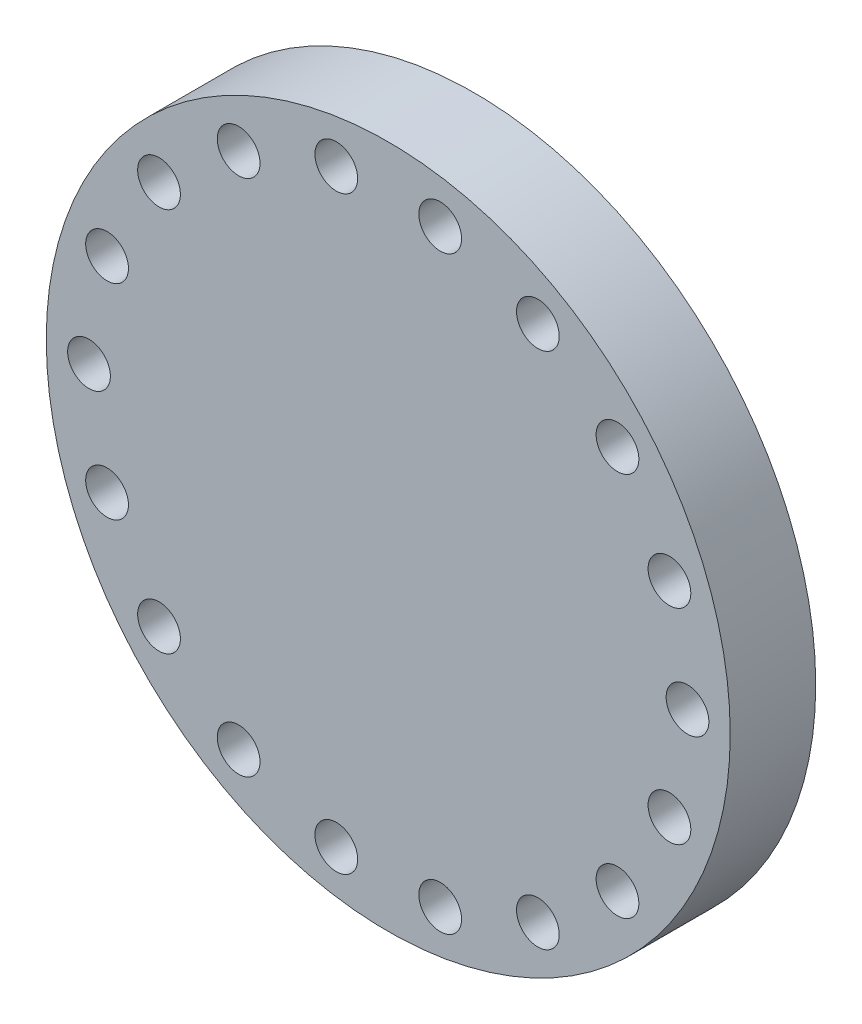
SolidWorks part; units mm, degrees
ref_plane "Front Plane" through (0, 0, 0) normal (0, 0, 1) x (1, 0, 0)
ref_plane "Top Plane" through (0, 0, 0) normal (0, 1, 0) x (1, 0, 0)
ref_plane "Right Plane" through (0, 0, 0) normal (1, 0, 0) x (0, 0, -1)
sketch "Sketch1" plane through (0, 0, 0) normal (0, 0, 1) x (1, 0, 0)
  line L0 (0, 0) -> (-44.45, 0) construction
  line L1 (0, 0) -> (-41.7693, 15.2028) construction
  circle A0 centre (0, 0) radius 50.8
  circle A1 centre (-44.45, 0) radius 3.175
  circle A2 centre (-41.7693, 15.2028) radius 3.175
  circle A3 centre (-34.0507, 28.5719) radius 3.175
  circle A4 centre (-22.225, 38.4948) radius 3.175
  circle A5 centre (-7.7187, 43.7747) radius 3.175
  circle A6 centre (7.7187, 43.7747) radius 3.175
  circle A7 centre (22.225, 38.4948) radius 3.175
  circle A8 centre (34.0507, 28.5719) radius 3.175
  circle A9 centre (41.7693, 15.2028) radius 3.175
  circle A10 centre (44.45, 0) radius 3.175
  circle A11 centre (41.7693, -15.2028) radius 3.175
  circle A12 centre (34.0507, -28.5719) radius 3.175
  circle A13 centre (22.225, -38.4948) radius 3.175
  circle A14 centre (7.7187, -43.7747) radius 3.175
  circle A15 centre (-7.7187, -43.7747) radius 3.175
  circle A16 centre (-22.225, -38.4948) radius 3.175
  circle A17 centre (-34.0507, -28.5719) radius 3.175
  circle A18 centre (-41.7693, -15.2028) radius 3.175
  point P3 (-44.45, 0)
  point P4 (0, 0)
  point P5 (-50.8, 0)
  point P50 (0, 0)
  point P51 (0, 0)
  dimension "D1" = 101.6
  dimension "D3" = 6.35
  dimension "D2" = 6.35
  dimension "D5" = 44.45
  dimension "D6" = 20
  dimension "D4" = 18
extrude "Boss-Extrude2" add sketch "Sketch1" against normal blind 12.7 contours A0
extrude "Cut-Extrude1" cut sketch "Sketch1<7>" against normal blind 12.7 contours A1 | A2 | A3 | A4 | A5 | A6 | A7 | A8 | A9 | A10 | A11 | A12 | A13 | A14 | A15 | A16 | A17 | A18
sketch "Sketch1<7>" plane through (0, 0, 0) normal (0, 0, 1) x (1, 0, 0) same geometry as "Sketch1"
